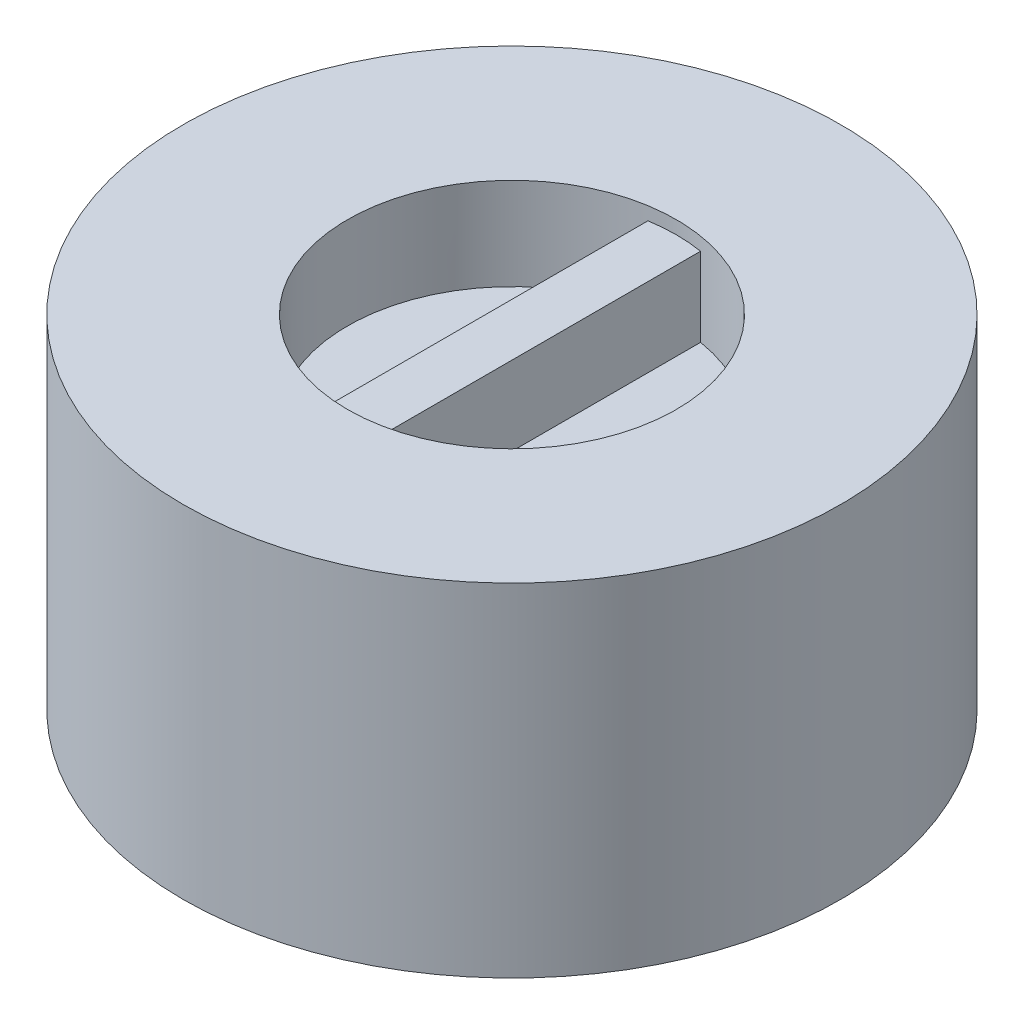
SolidWorks part; units mm, degrees
ref_plane "前视基准面" through (0, 0, 0) normal (0, 0, 1) x (1, 0, 0)
ref_plane "上视基准面" through (0, 0, 0) normal (0, 1, 0) x (1, 0, 0)
ref_plane "右视基准面" through (0, 0, 0) normal (1, 0, 0) x (0, 0, -1)
other "Configuration Table"
sketch "草图1" plane through (0, 0, 0) normal (0, 1, 0) x (1, 0, 0)
  line L0 (1, 1.3124) -> (1, -1.3124)
  circle A0 centre (0, 0) radius 2.5
  circle A1 centre (0, 0) radius 1.65
  dimension "D1" = 3.3
  dimension "D2" = 5
  dimension "D3" = 1
extrude "凸台-拉伸1" add sketch "草图1" along normal blind 0.5 contours A0
extrude "凸台-拉伸2" add sketch "草图1<3>" against normal blind 1.4 contours A0 A1 | L0 A1 region at (1.265, 0, 0) region at (-2.4293, 0, 0)
sketch "草图1<3>" plane through (0, 0, 0) normal (0, 1, 0) x (1, 0, 0) same geometry as "草图1"
sketch "草图2" plane through (0, 0.5, 0) normal (0, 1, 0) x (1, 0, 0)
  line L1 (-0.2, -1.25) -> (0.2, -1.25)
  line L2 (-0.2, -1.25) -> (-0.2, 1.25)
  line L3 (-0.2, 1.25) -> (0.2, 1.25)
  line L4 (0.2, -1.25) -> (0.2, 1.25)
  line L5 (-0.2, -1.25) -> (0.2, 1.25) construction
  line L6 (-0.2, 1.25) -> (0.2, -1.25) construction
  circle A1 centre (0, 0) radius 1.25
  circle A2 centre (0, 0) radius 2.5
  point P0 (0, 0)
  dimension "D2" = 5
  dimension "D3" = 2.5
  dimension "D1" = 0.4
extrude "凸台-拉伸3" add sketch "草图2" along normal blind 0.6 contours L2 L3 L4 L1
extrude "凸台-拉伸4" add sketch "草图2<3>" along normal blind 0.7 contours A1 | A2
sketch "草图2<3>" plane through (0, 0.5, 0) normal (0, 1, 0) x (1, 0, 0) same geometry as "草图2"
